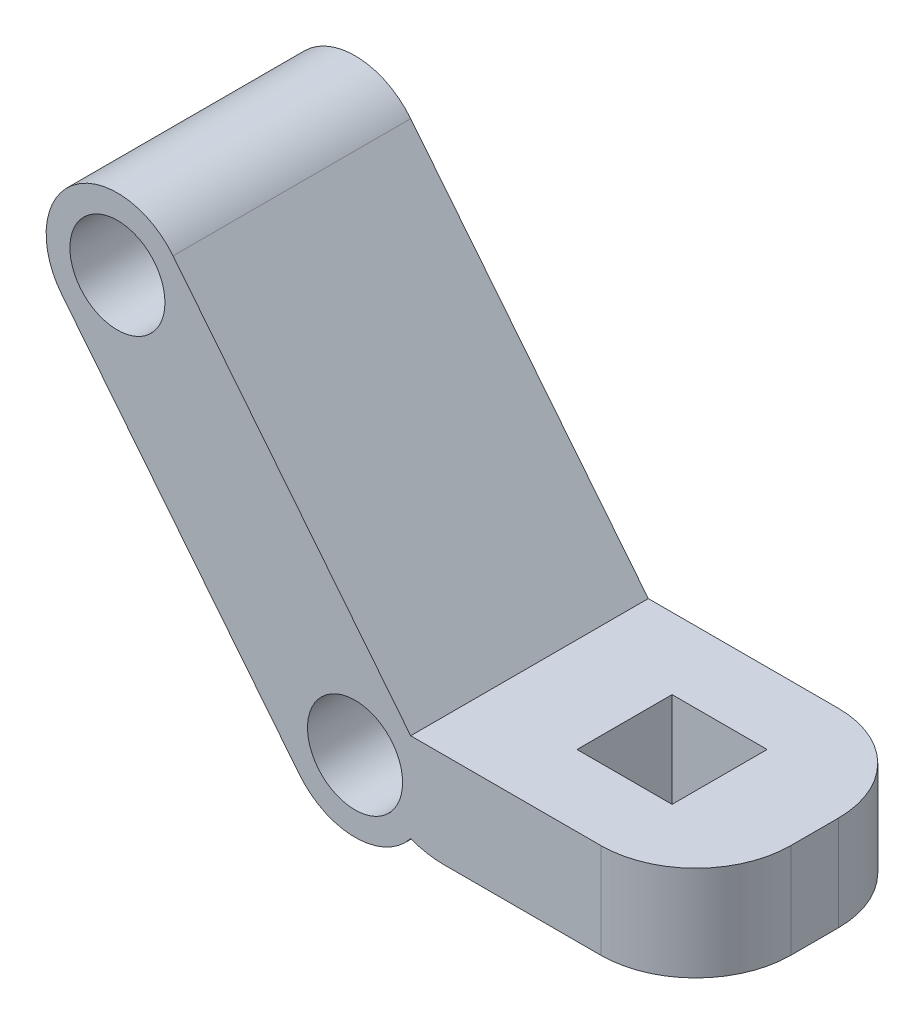
SolidWorks part; units mm, degrees
ref_plane "前视基准面" through (0, 0, 0) normal (0, 0, 1) x (1, 0, 0)
ref_plane "上视基准面" through (0, 0, 0) normal (0, 1, 0) x (1, 0, 0)
ref_plane "右视基准面" through (0, 0, 0) normal (1, 0, 0) x (0, 0, -1)
other "Configuration Table"
sketch "草图1" plane through (0, 0, 0) normal (0, 0, 1) x (1, 0, 0)
  line L0 (-30.8547, 26.5375) -> (-5.8547, -4.6875) construction
  line L1 (-25, 31.225) -> (0, 0)
  line L2 (-36.7094, 21.85) -> (-11.7094, -9.375)
  arc A0 (-25, 31.225) -> (-36.7094, 21.85) centre (-30.8547, 26.5375) ccw
  arc A1 (-11.7094, -9.375) -> (0, 0) centre (-5.8547, -4.6875) ccw
  point P2 (-18.3547, 10.925)
  dimension "D2" = 7.5
  dimension "D1" = 40
  dimension "D3" = 25
extrude "凸台-拉伸1" add sketch "草图1" along normal blind 25
sketch "草图2" plane through (0, 0, 25) normal (0, 0, 1) x (1, 0, 0)
  circle A0 centre (-30.8547, 26.5375) radius 5
  circle A1 centre (-5.8547, -4.6875) radius 5
  dimension "D1" = 10
extrude "切除-拉伸1" cut sketch "草图2" against normal through all
sketch "草图6" plane through (0, 0, 0) normal (0, 1, 0) x (1, 0, 0)
  line L0 (-11.7094, -25) -> (1.6453, -25) construction
  line L1 (0, 0) -> (30, 0)
  line L2 (0, 0) -> (0, -25)
  line L3 (0, -25) -> (30, -25)
  line L4 (30, 0) -> (30, -25)
  line L5 (0, -25) -> (0, 0) construction
  dimension "D1" = 30
extrude "凸台-拉伸2" add sketch "草图6" against normal blind 10
sketch "草图7" plane through (0, 0, 0) normal (0, 1, 0) x (1, 0, 0)
  line L2 (30, -25) -> (30, 0) construction
  line L3 (10, -17.5) -> (20, -17.5)
  line L4 (10, -17.5) -> (10, -7.5)
  line L5 (10, -7.5) -> (20, -7.5)
  line L6 (20, -17.5) -> (20, -7.5)
  line L7 (10, -17.5) -> (20, -7.5) construction
  line L8 (10, -7.5) -> (20, -17.5) construction
  line L9 (30, 0) -> (0, 0) construction
  point P0 (15, -12.5)
  dimension "D1" = 15
  dimension "D2" = 12.5
  dimension "D4" = 10
  dimension "D5" = 10
extrude "切除-拉伸2" cut sketch "草图7" against normal blind 10
fillet "圆角1" radius 10 2 edges at (30, -5, 0) (30, -5, 25)
fillet "圆角2" radius 10 1 edges at (0, -10, 12.5)
